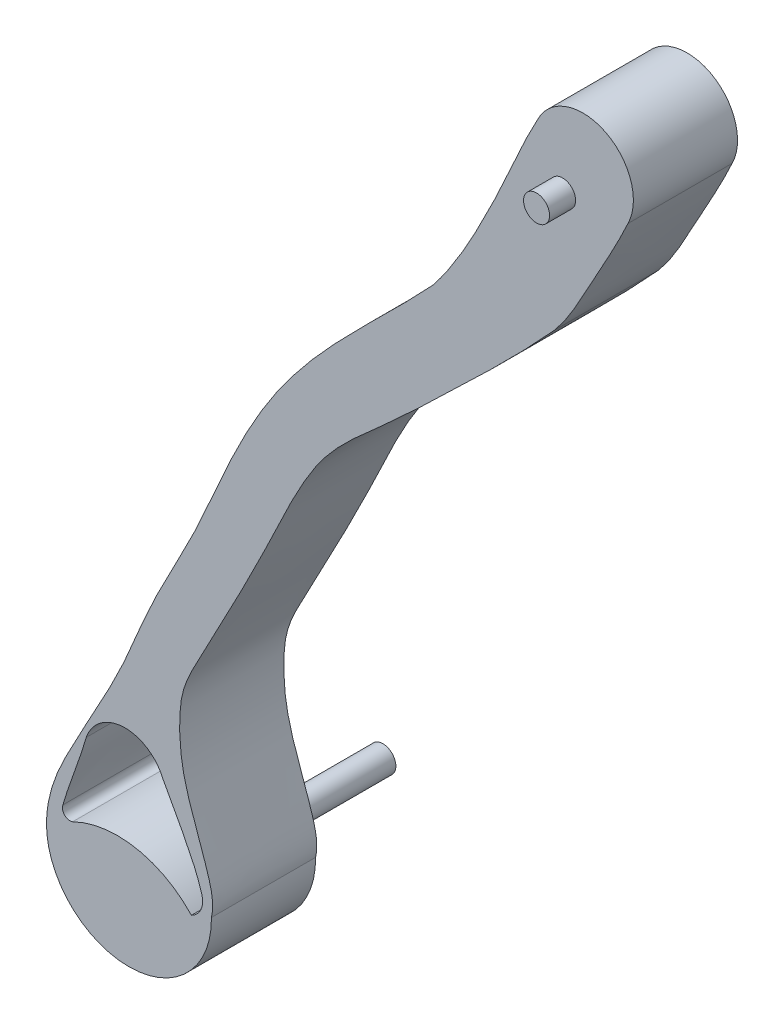
SolidWorks part; units mm, degrees
ref_plane "Front Plane" through (0, 0, 0) normal (0, 0, 1) x (1, 0, 0)
ref_plane "Top Plane" through (0, 0, 0) normal (0, 1, 0) x (1, 0, 0)
ref_plane "Right Plane" through (0, 0, 0) normal (1, 0, 0) x (0, 0, -1)
sketch "Sketch1" plane through (0, 0, 0) normal (0, 0, 1) x (1, 0, 0)
  line L0 (-958.0425, 331.2451) -> (-108.0425, 331.2451) construction
  line L1 (-128.5107, -145.2932) -> (-128.3596, -136.483) construction
  arc A0 (-128.4353, -140.8969) -> (-65.075, -140.8969) centre (-96.7551, -141.4405) ccw
  arc A1 (94.8965, 169.931) -> (60.3872, 187.5427) centre (77.6418, 178.7368) ccw
  spline S0 degree 3 poles (19.939, 111.9522) (3.6523, 94.329) (-20.2496, 73.6219) (-45.6524, 39.0411) (-58.8426, 13.6097) (-71.7895, -18.072) (-87.7389, -45.5003) (-100.8634, -79.9214) (-115.4521, -103.7884) (-126.1439, -125.77) (-128.3402, -135.3537) (-128.4353, -140.8969) knots 0 0 0 0 0.227861 0.297083 0.405626 0.498416 0.621398 0.705378 0.846798 0.885361 0.937345 0.937345 0.937345 0.937345
  spline S1 degree 3 poles (-65.075, -140.8969) (-63.9077, -135.8746) (-66.351, -126.6592) (-71.6977, -112.1281) (-76.3347, -98.4722) (-77.5417, -84.2072) (-76.962, -70.3421) (-68.8858, -55.695) (-58.2138, -35.3055) (-45.1098, -10.2853) (-33.8512, 14.9393) (-19.4413, 38.7618) (0.3461, 54.8463) (30.1497, 83.3531) (52.0053, 104.156) (66.8759, 120.5503) knots 0 0 0 0 0.04687 0.090142 0.148581 0.183457 0.2269 0.278591 0.340349 0.448131 0.547902 0.604794 0.712231 0.788345 1 1 1 1
  spline S2 degree 3 poles (66.8759, 120.5503) (72.3866, 127.1991) (81.1017, 144.0708) (90.5876, 160.476) (94.8965, 169.931) knots 0 0 0 0 0.452322 1 1 1 1
  spline S3 degree 3 poles (19.939, 111.9522) (26.2481, 119.8006) (36.0718, 136.3931) (48.5414, 162.1802) (55.829, 179.3017) (60.3872, 187.5427) knots 0 0 0 0 0.350646 0.671543 1 1 1 1
extrude "Boss-Extrude1" add sketch "Sketch1" along normal blind 40
sketch "Sketch2" plane through (0, 0, 0) normal (0, 0, -1) x (-1, 0, 0)
  arc A2 (68.7561, -135.1012) -> (72.7672, -144.0007) centre (76.035, -137.1742) ccw
  arc A3 (118.4099, -135.7129) -> (72.7672, -144.0007) centre (101.1511, -170.4908) ccw
  arc A4 (118.4099, -135.7129) -> (122.1174, -131.9212) centre (119.3954, -132.9681) ccw
  arc A5 (113.1744, -105.0297) -> (83.7676, -103.9711) centre (98.268, -110.1391) ccw
  spline S0 degree 3 poles (83.7676, -103.9711) (83.5874, -104.2987) (81.914, -107.3391) (79.5057, -111.7138) (76.6248, -117.1039) (74.515, -121.1655) (72.5234, -125.1819) (70.7511, -129.1745) (69.5362, -132.4779) (68.9336, -134.4701) (68.7561, -135.1012) knots 0.787262 0.787262 0.787262 0.787262 0.7908 0.820109 0.834763 0.849418 0.864072 0.878727 0.893381 0.900143 0.900143 0.900143 0.900143
  spline S1 degree 3 poles (122.1174, -131.9212) (121.9022, -131.1213) (121.4408, -129.5703) (120.6719, -127.1927) (119.6526, -124.1703) (118.3047, -120.3638) (116.0834, -114.194) (114.3135, -109.0461) (113.272, -105.3807) (113.1744, -105.0297) knots 0.0362 0.0362 0.0362 0.0362 0.044998 0.052823 0.060648 0.076298 0.091948 0.123247 0.12655 0.12655 0.12655 0.12655
sketch "Sketch3" plane through (0, 0, 40) normal (0, 0, 1) x (1, 0, 0)
  circle A1 centre (69.8194, 167.583) radius 5
extrude "Boss-Extrude3" add sketch "Sketch3" along normal blind 10
extrude "Cut-Extrude1" cut sketch "Sketch2" against normal blind 40
extrude "Boss-Extrude6" add sketch "Sketch3<2>" against normal blind 50
sketch "Sketch3<2>" plane through (0, 0, 40) normal (0, 0, 1) x (1, 0, 0) same geometry as "Sketch3"
sketch "Sketch4" plane through (0, 0, 40) normal (0, 0, 1) x (1, 0, 0)
  circle A0 centre (-99.2301, -155.1295) radius 5
  arc A3 (-122.1174, -131.9212) -> (-118.4099, -135.7129) centre (-119.3954, -132.9681) ccw construction
  point P2 (0, 0)
  point P9 (0, 0)
  point P13 (-121.4806, -135.007)
  dimension "D1" = 10
  dimension "D2" = 30
extrude "Boss-Extrude7" add sketch "Sketch4" against normal blind 100
